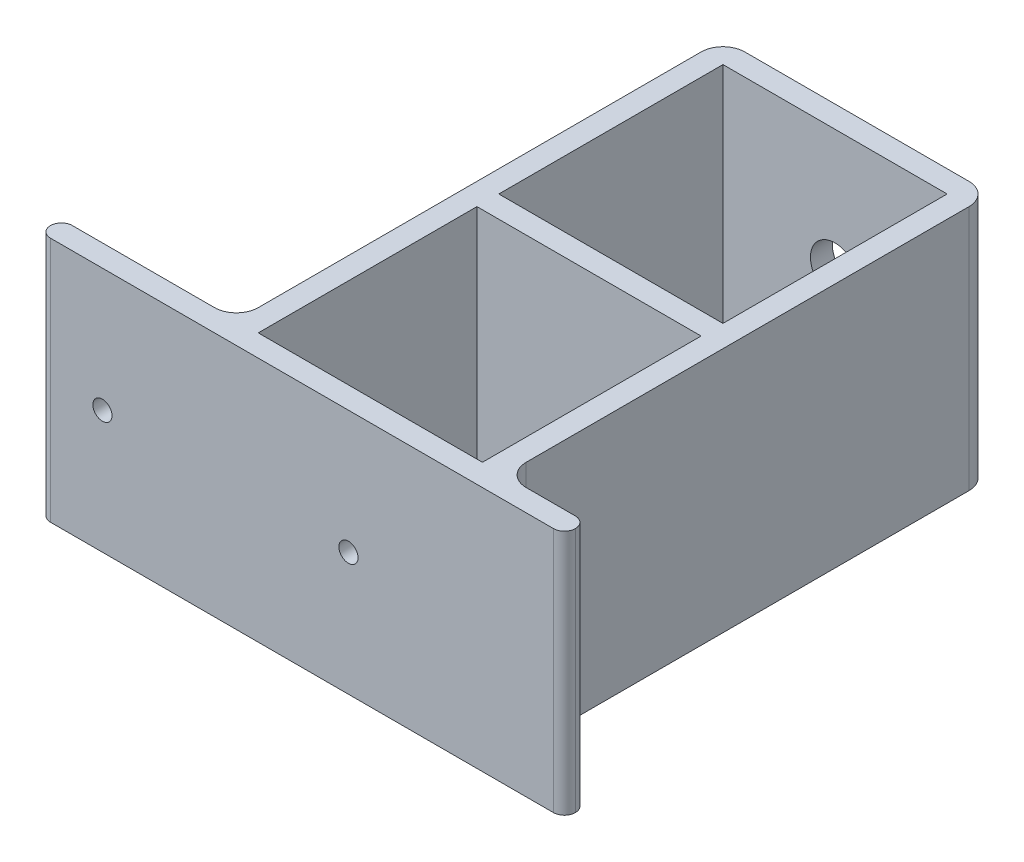
SolidWorks part; units mm, degrees
ref_plane "前视基准面" through (0, 0, 0) normal (0, 0, 1) x (1, 0, 0)
ref_plane "上视基准面" through (0, 0, 0) normal (0, 1, 0) x (1, 0, 0)
ref_plane "右视基准面" through (0, 0, 0) normal (1, 0, 0) x (0, 0, -1)
other "Configuration Table"
sketch "草图1" plane through (0, 0, 0) normal (0, 0, 1) x (1, 0, 0)
  line L0 (48, 0) -> (8.5, 0) construction
  line L1 (-48, -22.5) -> (48, -22.5)
  line L2 (-48, -22.5) -> (-48, 22.5)
  line L3 (-48, 22.5) -> (48, 22.5)
  line L4 (48, -22.5) -> (48, 22.5)
  line L5 (-48, -22.5) -> (48, 22.5) construction
  line L6 (-48, 22.5) -> (48, -22.5) construction
  circle A0 centre (8.5, 0) radius 1.75
  circle A1 centre (-36.5, 0) radius 1.75
  point P0 (0, 0)
  point P10 (-36.5, 0)
  point P12 (0, 0)
  dimension "D3" = 3.5
  dimension "D1" = 96
  dimension "D2" = 45
  dimension "D4" = 39.5
  dimension "D5" = 45
extrude "凸台-拉伸1" add sketch "草图1" along normal blind 4
sketch "草图2" plane through (0, 0, 0) normal (0, 0, -1) x (-1, 0, 0)
  line L0 (-48, 22.5) -> (48, 22.5) construction
  line L2 (-29, -22.5) -> (-29, 22.5)
  line L4 (12, -22.5) -> (12, 22.5)
  line L5 (-29, -22.5) -> (12, 22.5) construction
  line L6 (-29, 22.5) -> (12, -22.5) construction
  line L7 (48, -22.5) -> (-48, -22.5) construction
  line L8 (-8.5, -22.5) -> (-8.5, 22.5) construction
  line L9 (-29, 22.5) -> (-33, 22.5)
  line L10 (-33, 22.5) -> (-33, -22.5)
  line L11 (-33, -22.5) -> (-29, -22.5)
  line L12 (16, 22.5) -> (16, -22.5)
  line L13 (12, 22.5) -> (16, 22.5)
  line L14 (16, -22.5) -> (12, -22.5)
  point P0 (-8.5, 0)
  dimension "D1" = 41
  dimension "D2" = 4
extrude "凸台-拉伸2" add sketch "草图2" along normal blind 85
sketch "草图3" plane through (0, 0, -85) normal (0, 0, -1) x (-1, 0, 0)
  line L1 (-33, 22.5) -> (16, 22.5)
  line L2 (-33, 22.5) -> (-33, -22.5)
  line L3 (-33, -22.5) -> (16, -22.5)
  line L4 (16, 22.5) -> (16, -22.5)
extrude "凸台-拉伸3" add sketch "草图3" along normal blind 4
sketch "草图4" plane through (0, -22.5, 0) normal (0, -1, 0) x (1, 0, 0)
  line L0 (-12, -85) -> (-12, 0) construction
  line L1 (-12, -44) -> (29, -44)
  line L2 (-12, -44) -> (-12, -40)
  line L3 (-12, -40) -> (29, -40)
  line L4 (29, -44) -> (29, -40)
  line L5 (29, -85) -> (29, 0) construction
  line L6 (29, -85) -> (-12, -85) construction
  dimension "D1" = 4
  dimension "D2" = 41
extrude "凸台-拉伸4" add sketch "草图4" against normal up to surface (45 mm away) up to face at (8.5, 22.5, -42.5)
fillet "圆角1" radius 4 4 edges at (-16, 0, 0) (-16, 0, -89) (33, 0, -89) (33, 0, 0)
sketch "草图5" plane through (0, 0, -89) normal (0, 0, -1) x (-1, 0, 0)
  line L0 (-8.5, 22.5) -> (-8.5, -22.5) construction
  line L1 (12, 22.5) -> (-29, 22.5) construction
  line L2 (-29, -22.5) -> (12, -22.5) construction
  line L3 (-29, 0) -> (12, 0) construction
  line L4 (-29, 22.5) -> (-29, -22.5) construction
  line L5 (12, -22.5) -> (12, 22.5) construction
  circle A0 centre (-8.5, 0) radius 4.5
  dimension "D1" = 9
extrude "切除-拉伸1" cut sketch "草图5" against normal up to surface (4 mm away) up to face at (8.5, 0, -85)
fillet "圆角2" radius 2 4 edges at (-48, 0, 4) (-48, 0, 0) (48, 0, 4) (48, 0, 0)
